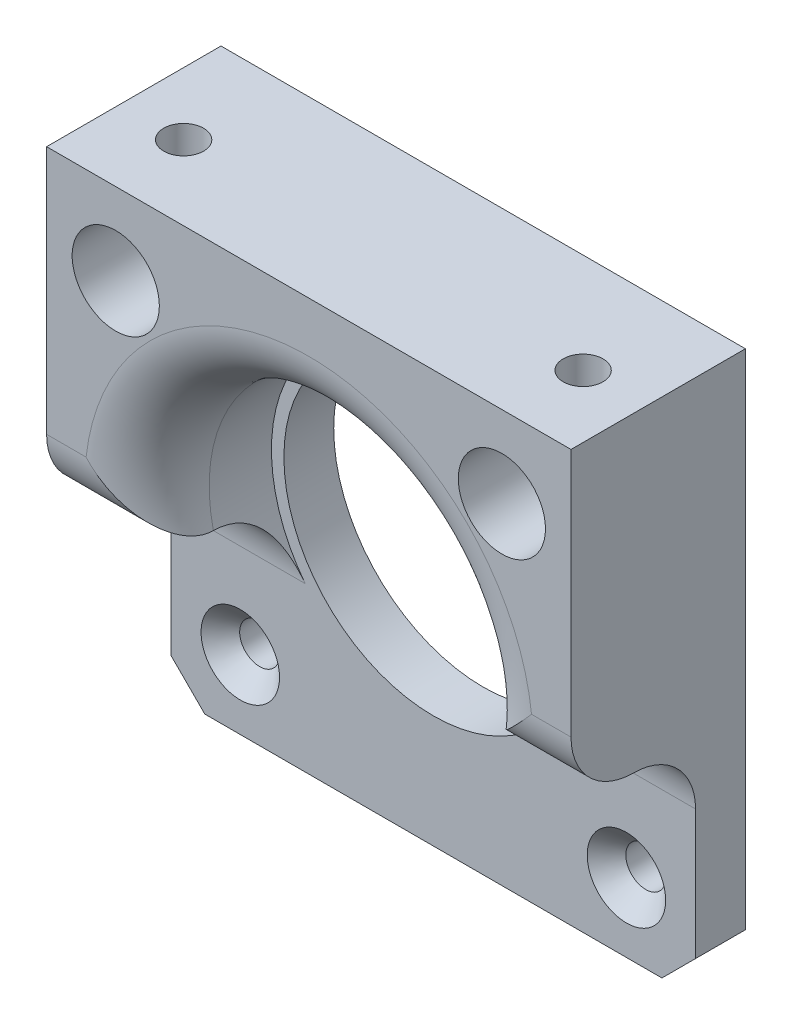
SolidWorks part; units mm, degrees
material "ABS"
ref_plane "Plano frontal" through (0, 0, 0) normal (0, 0, 1) x (1, 0, 0)
ref_plane "Plano superior" through (0, 0, 0) normal (0, 1, 0) x (1, 0, 0)
ref_plane "Plano direito" through (0, 0, 0) normal (1, 0, 0) x (0, 0, -1)
sketch "Esboço1" plane through (0, 0, 0) normal (0, 0, 1) x (1, 0, 0)
  line L1 (108.3727, -351.7657) -> (66.2727, -351.7657)
  line L2 (108.3727, -351.7657) -> (108.3727, -309.6657)
  line L3 (108.3727, -309.6657) -> (66.2727, -309.6657)
  line L4 (66.2727, -351.7657) -> (66.2727, -309.6657)
extrude "Ressalto-extrusão1" add sketch "Esboço1" along normal blind 4
sketch "Esboço2" plane through (0, 0, 4) normal (0, 0, 1) x (1, 0, 0)
  circle A1 centre (87.3227, -330.7157) radius 12
  dimension "D1" = 24
extrude "Corte-extrusão1" cut sketch "Esboço2" against normal blind 8
hole_wizard "Escareado para parafuso de máquina com cabeça chata de M31" positions "Esboço4" profile "Esboço3" countersink size "M3" standard "Ansi Metric" end condition through all
sketch "Esboço4" plane through (0, 0, 4) normal (0, 0, 1) x (1, 0, 0)
  point P0 (102.8227, -346.2157)
  point P3 (102.8227, -315.2157)
  point P6 (71.8227, -315.2157)
  point P9 (71.8227, -346.2157)
sketch "Esboço3" plane through (102.8227, -346.2157, 4) normal (1, 0, 0) x (0, -1, 0)
  line L0 (0, 0) -> (0, 4)
  line L1 (0, 4) -> (1.6, 4)
  line L2 (1.6, 4) -> (1.6, 1.55)
  line L3 (1.6, 1.55) -> (3.15, 0)
  line L5 (3.15, 0) -> (0, 0)
  line L6 (-1.6, 1.55) -> (-3.15, 0) construction
  line L11 (0, -6.35) -> (0, 107.95) construction
  dimension "Thru Hole Dia." = 3.2
  dimension "Thru Hole Depth" = 4
  dimension "Near C'Sink Dia." = 6.3
  dimension "Near C'Sink Angle" = 90
sketch "Esboço5" plane through (0, 0, 4) normal (0, 0, 1) x (1, 0, 0)
  line L0 (108.3727, -351.7657) -> (108.3727, -309.6657) construction
  line L5 (99.9836, -333.6657) -> (108.3727, -333.6657)
  line L6 (66.2727, -309.6657) -> (108.3727, -309.6657)
  line L7 (66.2727, -309.6657) -> (66.2727, -333.6657)
  line L8 (66.2727, -333.6657) -> (74.6618, -333.6657)
  line L9 (108.3727, -309.6657) -> (108.3727, -333.6657)
  arc A0 (99.9836, -333.6657) -> (74.6618, -333.6657) centre (87.3227, -330.7157) ccw
  dimension "D2" = 24
  dimension "D1" = 13
extrude "Ressalto-extrusão2" add sketch "Esboço5" along normal blind 10
sketch "Esboço6" plane through (0, 0, 14) normal (0, 0, 1) x (1, 0, 0)
  circle A0 centre (71.8227, -315.2157) radius 3.5
  circle A1 centre (102.8227, -315.2157) radius 3.5
extrude "Corte-extrusão2" cut sketch "Esboço6" against normal blind 10
hole_wizard "Furo com folga de M31" positions "Esboço8" profile "Esboço7" hole size "M3" standard "ISO" end condition through all
sketch "Esboço8" plane through (0, -309.6657, 0) normal (0, 1, 0) x (1, 0, 0)
  line L0 (87.3227, -14) -> (87.3227, 0) construction
  line L1 (108.3727, -14) -> (66.2727, -14) construction
  line L2 (108.3727, 0) -> (66.2727, 0) construction
  point P0 (103.3591, -8.0127)
  point P13 (71.2863, -8.0127)
sketch "Esboço7" plane through (103.3591, -309.6657, 8.0127) normal (1, 0, 0) x (0, 0, 1)
  line L0 (0, 0) -> (0, 42.1)
  line L1 (0, 42.1) -> (1.6, 42.1)
  line L2 (1.6, 42.1) -> (1.6, 0)
  line L5 (1.6, 0) -> (0, 0)
  line L11 (0, -6.35) -> (0, 107.95) construction
  dimension "Thru Hole Dia." = 3.2
  dimension "Thru Hole Depth" = 42.1
ref_plane "Plano1" through (0, -315.7657, 0) normal (0, -1, 0) x (-1, 0, 0)
sketch "Esboço9" plane through (0, -309.6657, 0) normal (0, -1, 0) x (1, 0, 0)
  line L0 (100.3227, 14) -> (74.3227, 14) construction
  line L1 (95.6994, 14) -> (78.946, 14)
  line L2 (95.6994, 14) -> (95.6994, 1.7904)
  line L3 (95.6994, 1.7904) -> (78.946, 1.7904)
  line L4 (78.946, 14) -> (78.946, 1.7904)
  line L6 (87.3227, 0) -> (87.3227, 14) construction
  line L8 (108.3727, 0) -> (66.2727, 0) construction
extrude "Corte-extrusão3" [suppressed] cut sketch "Esboço9" along normal blind 6
sketch "Esboço10" [suppressed] plane through (0, -315.6657, 0) normal (0, 1, 0) x (1, 0, 0)
  line L0 (83.9727, -5.5101) -> (83.9727, -8.3784) construction
  line L1 (84.9727, -5.5101) -> (84.9727, -8.3784)
  line L2 (82.9727, -5.5101) -> (82.9727, -8.3784)
  line L3 (90.6727, -5.5101) -> (90.6727, -8.3784) construction
  line L4 (91.6727, -5.5101) -> (91.6727, -8.3784)
  line L5 (89.6727, -5.5101) -> (89.6727, -8.3784)
  arc A0 (84.9727, -5.5101) -> (82.9727, -5.5101) centre (83.9727, -5.5101) ccw
  arc A1 (82.9727, -8.3784) -> (84.9727, -8.3784) centre (83.9727, -8.3784) ccw
  arc A2 (91.6727, -5.5101) -> (89.6727, -5.5101) centre (90.6727, -5.5101) ccw
  arc A3 (89.6727, -8.3784) -> (91.6727, -8.3784) centre (90.6727, -8.3784) ccw
  point P2 (83.9727, -6.9442)
  point P9 (90.6727, -6.9442)
  dimension "D1" = 1
  dimension "D2" = 1
extrude "Corte-extrusão4" [suppressed] cut sketch "Esboço10" against normal blind 45
sketch "Esboço12" [suppressed] plane through (0, -333.6657, 0) normal (0, -1, 0) x (1, 0, 0)
  line L0 (82.9727, 6.9442) -> (91.6727, 6.9442) construction
  line L1 (82.9727, 9.8885) -> (91.6727, 9.8885)
  line L2 (82.9727, 4) -> (91.6727, 4)
  line L3 (100.3227, 4) -> (74.3227, 4) construction
  line L4 (100.3227, 4) -> (74.3227, 4) construction
  line L7 (82.9727, 5.5101) -> (82.9727, 8.3784) construction
  line L8 (91.6727, 8.3784) -> (91.6727, 5.5101) construction
  arc A0 (82.9727, 9.8885) -> (82.9727, 4) centre (82.9727, 6.9442) ccw
  arc A1 (91.6727, 4) -> (91.6727, 9.8885) centre (91.6727, 6.9442) ccw
  point P4 (87.3227, 6.9442)
extrude "Corte-extrusão5" [suppressed] cut sketch "Esboço12" against normal blind 16.5
fillet "Filete1" radius 5 5 edges at (87.3227, -317.7157, 14) (104.1781, -333.6657, 14) (70.4673, -333.6657, 14)
fillet "Filete2" [suppressed] radius 0.5
sketch "Esboço13" plane through (0, -351.7657, 0) normal (0, -1, 0) x (1, 0, 0)
  line L1 (74.0363, 9.6004) -> (71.2863, 11.1881)
  line L2 (71.2863, 11.1881) -> (68.5363, 9.6004)
  line L3 (68.5363, 9.6004) -> (68.5363, 6.4249)
  line L4 (68.5363, 6.4249) -> (71.2863, 4.8372)
  line L5 (71.2863, 4.8372) -> (74.0363, 6.4249)
  line L6 (74.0363, 6.4249) -> (74.0363, 9.6004)
  line L7 (106.1091, 9.6004) -> (103.3591, 11.1881)
  line L8 (103.3591, 11.1881) -> (100.6091, 9.6004)
  line L9 (100.6091, 9.6004) -> (100.6091, 6.4249)
  line L10 (100.6091, 6.4249) -> (103.3591, 4.8372)
  line L11 (103.3591, 4.8372) -> (106.1091, 6.4249)
  line L12 (106.1091, 6.4249) -> (106.1091, 9.6004)
  circle A2 centre (71.2863, 8.0127) radius 2.75 construction
  circle A3 centre (103.3591, 8.0127) radius 2.75 construction
extrude "Corte-extrusão6" cut sketch "Esboço13" against normal blind 22.5
chamfer "Chanfro1" distance 2.7 angle 45 2 edges at (66.2727, -351.7657, 2) (108.3727, -351.7657, 2)
chamfer "Chanfro2" [suppressed] distance 0.1 angle 45
sketch "Esboço14" plane through (0, -309.6657, 0) normal (0, 1, 0) x (1, 0, 0)
  line L1 (66.2727, -14) -> (73.7769, -14)
  line L2 (66.2727, -14) -> (66.2727, -11.5964)
  line L3 (66.2727, -11.5964) -> (73.7769, -11.5964)
  line L4 (73.7769, -14) -> (73.7769, -11.5964)
  spline S0 degree 3 poles (69.4398, -14) (69.5727, -14) (69.7086, -13.9932) (69.9783, -13.9667) (70.1135, -13.9469) (70.5199, -13.8685) (70.7932, -13.7906) (71.6105, -13.4813) (72.1417, -13.183) (72.9065, -12.5724) (73.1545, -12.3413) (73.5003, -11.9557) (73.6116, -11.8203) (73.8248, -11.5335) (73.9271, -11.3813) (74.1172, -11.0616) (74.2044, -10.8953) (74.3603, -10.5478) (74.4293, -10.3656) (74.5999, -9.7988) (74.6618, -9.4073) (74.6618, -9) knots 0 0 0 0 0.0625 0.0625 0.125 0.125 0.25 0.25 0.5 0.5 0.625 0.625 0.6875 0.6875 0.75 0.75 0.8125 0.8125 0.875 0.875 1 1 1 1 construction
extrude "Corte-extrusão7" [suppressed] cut sketch "Esboço14" against normal through all
sketch "Sketch2" plane through (0, -309.6657, 0) normal (0, 1, 0) x (1, 0, 0)
  line L9 (66.2727, -14) -> (108.3727, -14)
  line L10 (108.3727, -14) -> (108.3727, 0)
  line L11 (108.3727, 0) -> (66.2727, 0)
  line L12 (66.2727, 0) -> (66.2727, -14)
  line L17 (66.2727, -14) -> (108.3727, -14)
  line L18 (108.3727, -14) -> (108.3727, 0)
  line L19 (108.3727, 0) -> (66.2727, 0)
  line L20 (66.2727, 0) -> (66.2727, -14)
  circle A0 centre (71.2863, -8.0127) radius 1.6 construction
  circle A1 centre (103.3591, -8.0127) radius 1.6 construction
  circle A2 centre (71.2863, -8.0127) radius 1.6
  circle A3 centre (103.3591, -8.0127) radius 1.6
  dimension "D1" = 0
extrude "Boss-Extrude1" add sketch "Sketch2" along normal blind 1
chamfer "Chanfro3" [suppressed] distance 0.1 angle 45
sketch "Sketch3" plane through (0, 0, 14) normal (0, 0, 1) x (1, 0, 0)
  line L1 (66.2727, -308.6657) -> (79.2727, -308.6657)
  line L2 (66.2727, -308.6657) -> (66.2727, -311.7157)
  line L3 (66.2727, -311.7157) -> (79.2727, -311.7157)
  line L7 (79.2727, -311.7157) -> (79.2727, -308.6657)
  dimension "13" = 13
extrude "Boss-Extrude2" [suppressed] add sketch "Sketch3" along normal blind 5.5 and the other way blind 3.6
fillet "Fillet1" [suppressed] radius 6
fillet "Fillet2" [suppressed] radius 3
sketch "Sketch4" [suppressed] plane through (0, -351.7657, 0) normal (0, -1, 0) x (1, 0, 0)
  line L1 (79.2727, 19.5) -> (74.8946, 19.5)
  line L2 (79.2727, 19.5) -> (79.2727, 17.6667)
  line L3 (79.2727, 17.6667) -> (74.8946, 17.6667)
  line L4 (74.8946, 19.5) -> (74.8946, 17.6667)
extrude "Cut-Extrude1" [suppressed] cut sketch "Sketch4" against normal blind 49
